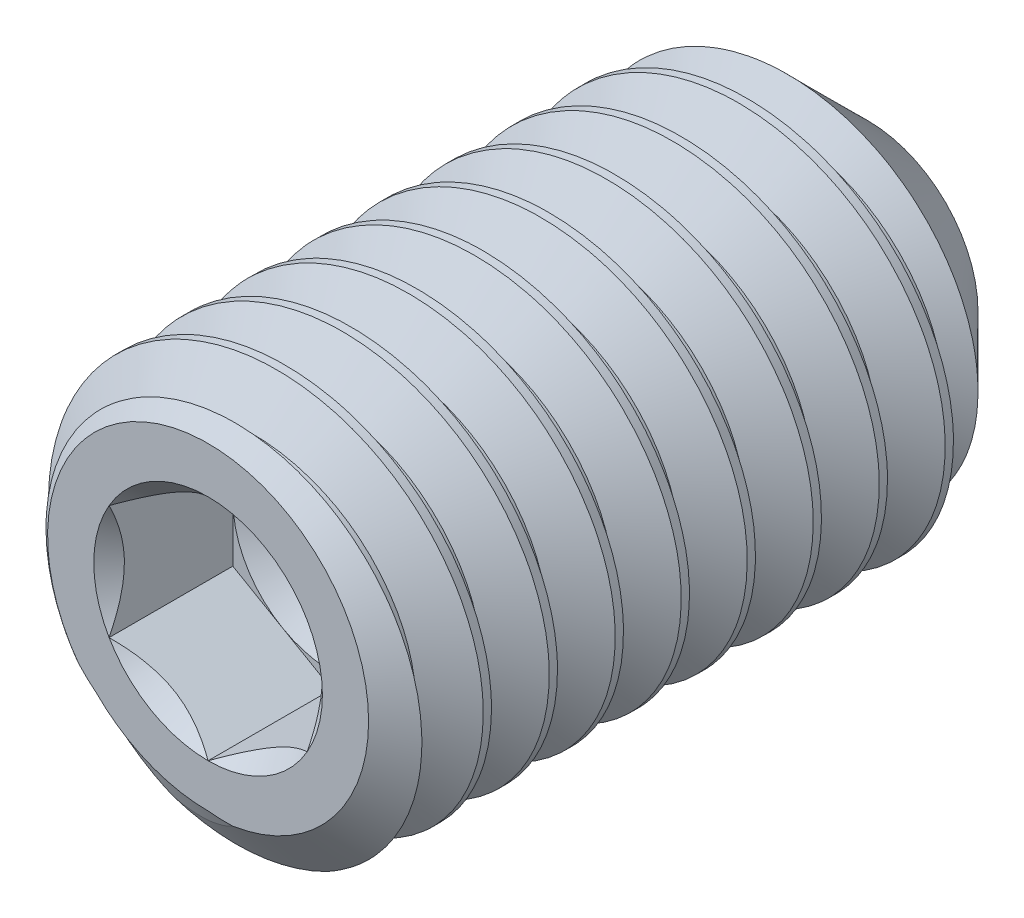
SolidWorks part; units mm, degrees
ref_plane "Front" through (0, 0, 0) normal (0, 0, 1) x (1, 0, 0)
ref_plane "Top" through (0, 0, 0) normal (0, 1, 0) x (1, 0, 0)
ref_plane "Right" through (0, 0, 0) normal (1, 0, 0) x (0, 0, -1)
sketch "Sketch22" plane through (0, 0, 0) normal (1, 0, 0) x (0, 0, -1)
  line L0 (-3.5715, 0) -> (-3.5715, 1.9304)
  line L1 (-3.5715, 1.9304) -> (-3.2336, 2.413)
  line L2 (-3.2336, 2.413) -> (3.2752, 2.413)
  line L3 (3.2752, 2.413) -> (4.366, 1.3222)
  line L4 (4.366, 1.3222) -> (3.5715, 0)
  line L5 (3.5715, 0) -> (-3.5715, 0)
  line L6 (3.5715, 0) -> (4.366, 0) construction
  line L7 (4.366, 0) -> (4.366, 1.3222) construction
  line L8 (4.366, -1.3222) -> (3.5715, 0) construction
  line L9 (-3.2336, -2.413) -> (3.2752, -2.413) construction
  line L10 (4.366, -2.413) -> (4.366, 2.413) construction
  line L11 (4.366, 2.413) -> (3.5722, 2.413) construction
  point P11 (2.3816, -2.413)
  point P15 (4.366, 0)
  dimension "D3" = 35
  dimension "D5" = 118
  dimension "D6" = 45
  dimension "D7" = 3.8608
  dimension "D1" = 1.9844
revolve "Revolve1" add sketch "Sketch22" angle 360 about L6
ref_plane "Plane1" through (0, 0, -4.366) normal (0, 0, 1) x (1, 0, 0)
sketch "Sketch27" plane through (0, 0, -4.366) normal (0, 0, 1) x (1, 0, 0)
  circle A0 centre (0, 0) radius 2.413 construction
  circle A1 centre (0, 0) radius 2.413
sketch "Sketch23" plane through (0, 0, 3.5715) normal (0, 0, 1) x (1, 0, 0)
  line L1 (0, 1.3748) -> (-1.1906, 0.6874)
  line L2 (-1.1906, 0.6874) -> (-1.1906, -0.6874)
  line L3 (-1.1906, -0.6874) -> (0, -1.3748)
  line L4 (0, -1.3748) -> (1.1906, -0.6874)
  line L5 (1.1906, -0.6874) -> (1.1906, 0.6874)
  line L6 (1.1906, 0.6874) -> (0, 1.3748)
  circle A0 centre (0, 0) radius 1.1906 construction
extrude "Cut-Extrude10" cut sketch "Sketch23" against normal blind 1.4883
sketch "Sketch24" plane through (0, 0, 3.5715) normal (0, 0, 1) x (1, 0, 0)
  circle A0 centre (0, 0) radius 1.3748
extrude "Cut-Extrude11" cut sketch "Sketch24" against normal through all draft 45
sketch "Sketch26" plane through (0, 0, 2.0832) normal (0, 0, 1) x (1, 0, 0)
  circle A0 centre (0, 0) radius 1.1906 construction
  circle A1 centre (0, 0) radius 1.1906
extrude "Cut-Extrude12" cut sketch "Sketch26" against normal through all draft 60
sketch "Sketch31" plane through (0, 0, 0) normal (1, 0, 0) x (0, 0, -1)
  line L2 (3.5715, 0) -> (4.366, -1.3222)
  line L3 (4.366, 1.3222) -> (3.5715, 0)
ref_axis "Center Axis1" through (0, 0, -42.9554) along (0, 0, 1)
ref_plane "Contact Plane1" through (0, 0, -4.366) normal (0, 0, 1) x (1, 0, 0)
ref_plane "Contact Plane2" through (0, 0, 3.5715) normal (0, 0, 1) x (1, 0, 0)
curve "Helix/Spiral1" pitch 0.7937 height 8.7312 radius 2.413 centre (0, 0, -4.366) axis (0, 0, 1) start towards (0, 1, 0)
sketch "Sketch32" plane through (0, 0, 0) normal (1, 0, 0) x (0, 0, -1)
  line L0 (4.3164, 2.4989) -> (5.1101, 2.4989) construction
  line L1 (5.1101, 2.4989) -> (4.7133, 1.8115) construction
  line L2 (4.7133, 1.8115) -> (4.3164, 2.4989) construction
  line L3 (4.366, 2.413) -> (3.5722, 2.413) construction
  line L4 (4.7133, 1.8115) -> (4.7133, 1.8974) construction
  line L5 (4.7133, 2.4989) -> (4.7133, 2.413) construction
  line L6 (4.6636, 1.8974) -> (4.7629, 1.8974)
  line L7 (4.366, 2.413) -> (5.0605, 2.413) construction
  line L8 (4.3412, 2.456) -> (5.0853, 2.456)
  line L9 (4.3412, 2.456) -> (4.6636, 1.8974)
  line L10 (4.7629, 1.8974) -> (5.0853, 2.456)
  point P11 (4.7133, 1.8974)
  point P13 (4.7133, 2.413)
  point P17 (4.7133, 2.456)
  dimension "D1" = 0.0992
sweep "Cut-Sweep1" cut profiles "Sketch32" path "Helix/Spiral1"
equation "\"D7@Sketch22\"=\"Dia@Sketch22\"*.8"
equation "\"D3@Helix/Spiral1\"=\"Length@Sketch22\" + \"Pitch@Sketch22\"l1\""
equation "\"hex Depth@Cut-Extrude10\" = \"Hex@Sketch23\" * .625"
equation "\"D1@Sketch22\"=\"Pitch@Sketch22\"*2.5"
equation "\"D4@Helix/Spiral1\"=\"Pitch@Sketch22\""
equation "\"D1@Sketch32\"=\"Pitch@Sketch22\"*.125"
